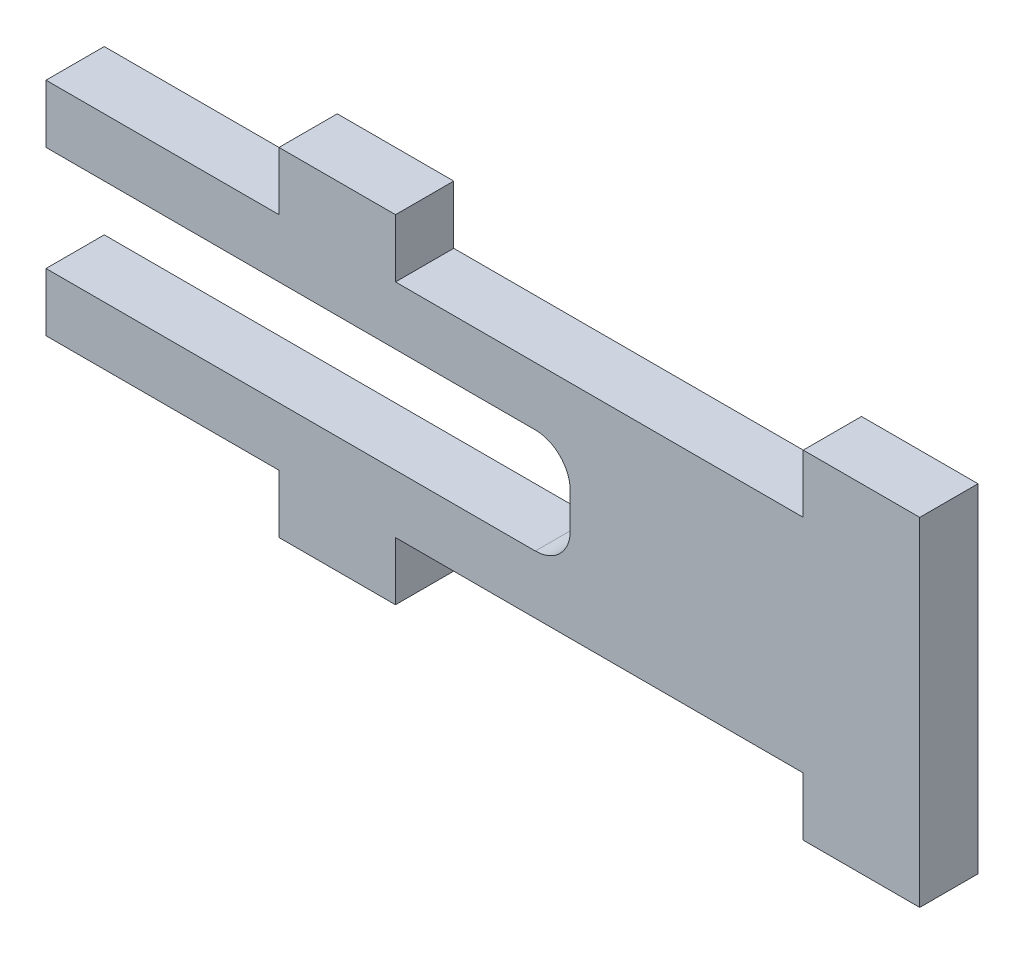
SolidWorks part; units mm, degrees
material "6061-T4 (SS)"
ref_plane "Front Plane" through (0, 0, 0) normal (0, 0, 1) x (1, 0, 0)
ref_plane "Top Plane" through (0, 0, 0) normal (0, 1, 0) x (1, 0, 0)
ref_plane "Right Plane" through (0, 0, 0) normal (1, 0, 0) x (0, 0, -1)
sketch "Sketch2" plane through (0, 0, 0) normal (0, 0, 1) x (1, 0, 0)
  line L0 (0, 0) -> (-65.1233, 0) construction
  line L1 (0, -14.5) -> (0, 14.5)
  line L2 (0, 14.5) -> (-10, 14.5)
  line L3 (-10, 14.5) -> (-10, 9.5)
  line L4 (-10, 9.5) -> (-45, 9.5)
  line L5 (-45, 9.5) -> (-45, 14.5)
  line L6 (-45, 14.5) -> (-55, 14.5)
  line L7 (-55, 14.5) -> (-55, 9.5)
  line L8 (-55, 9.5) -> (-75, 9.5)
  line L9 (-75, 9.5) -> (-75, 4.5)
  line L10 (-75, 4.5) -> (-33, 4.5)
  line L11 (-30, 1.5) -> (-30, 0)
  line L12 (-30, -1.5) -> (-30, 0)
  line L13 (-75, -4.5) -> (-33, -4.5)
  line L14 (-75, -9.5) -> (-75, -4.5)
  line L15 (-55, -9.5) -> (-75, -9.5)
  line L16 (-55, -14.5) -> (-55, -9.5)
  line L17 (-45, -14.5) -> (-55, -14.5)
  line L18 (-45, -9.5) -> (-45, -14.5)
  line L19 (-10, -9.5) -> (-45, -9.5)
  line L20 (-10, -14.5) -> (-10, -9.5)
  line L21 (0, -14.5) -> (-10, -14.5)
  arc A0 (-33, 4.5) -> (-30, 1.5) centre (-33, 1.5) cw
  arc A1 (-33, -4.5) -> (-30, -1.5) centre (-33, -1.5) ccw
  point P17 (-30, 0.75)
  dimension "D1" = 35
  dimension "D7" = 3
  dimension "D2" = 10
  dimension "D3" = 20
  dimension "D4" = 5
  dimension "D5" = 45
  dimension "D6" = 10
  dimension "D8" = 5
  dimension "D9" = 29
extrude "Boss-Extrude1" add sketch "Sketch2" along normal blind 5
